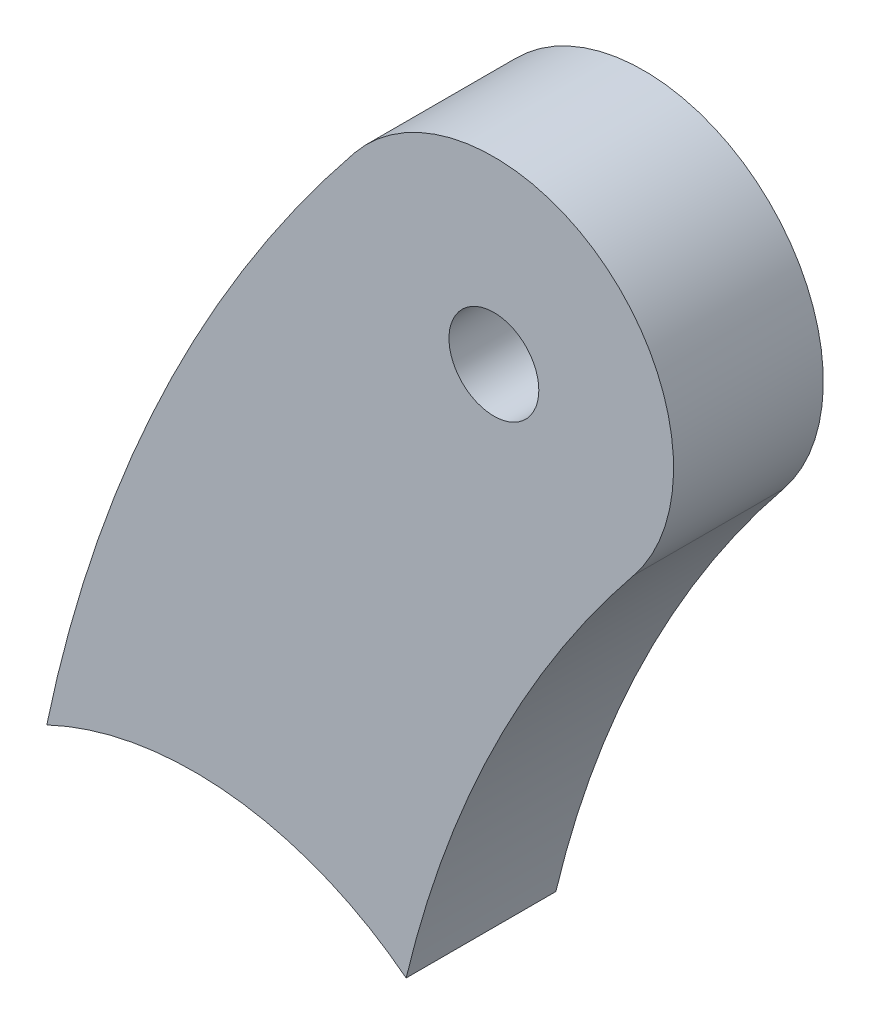
SolidWorks part; units mm, degrees
ref_plane "Plan de face" through (0, 0, 0) normal (0, 0, 1) x (1, 0, 0)
ref_plane "Plan de dessus" through (0, 0, 0) normal (0, 1, 0) x (1, 0, 0)
ref_plane "Plan de droite" through (0, 0, 0) normal (1, 0, 0) x (0, 0, -1)
sketch "Esquisse1" plane through (0, 0, 0) normal (0, 0, 1) x (1, 0, 0)
  line L0 (-35, 28.2843) -> (0, 0) construction
  line L1 (0, 0) -> (-45, 0) construction
  line L2 (-47.0298, -1.0204) -> (-35.9733, 30.2522) construction
  line L3 (0, 0) -> (-42.4264, 15) construction
  arc A0 (-45, 0) -> (-35, 28.2843) centre (0, 0) cw construction
  arc A1 (-39.6667, 32.0555) -> (-49.9306, 10.3894) centre (0, 0) ccw
  arc A2 (-30.3333, 24.513) -> (-37.9306, 9.0704) centre (0, 0) ccw
  arc A3 (-30.3333, 24.513) -> (-39.6667, 32.0555) centre (-35, 28.2843) ccw
  arc A4 (-49.9306, 10.3894) -> (-37.9306, 9.0704) centre (-45, 0) cw
  circle A5 centre (-35, 28.2843) radius 1.5
  circle A6 centre (-45, 0) radius 1.5 construction
  circle A7 centre (-45, 0) radius 11.5 construction
  point P4 (-42.4264, 15)
  dimension "D1" = 30
  dimension "D2" = 3
  dimension "D3" = 6
  dimension "D4" = 45
  dimension "D6" = 23
  dimension "D7" = 51
  dimension "D8" = 39
  dimension "D5" = 1
extrude "Boss.-Extru.1" add sketch "Esquisse1" along normal blind 5
